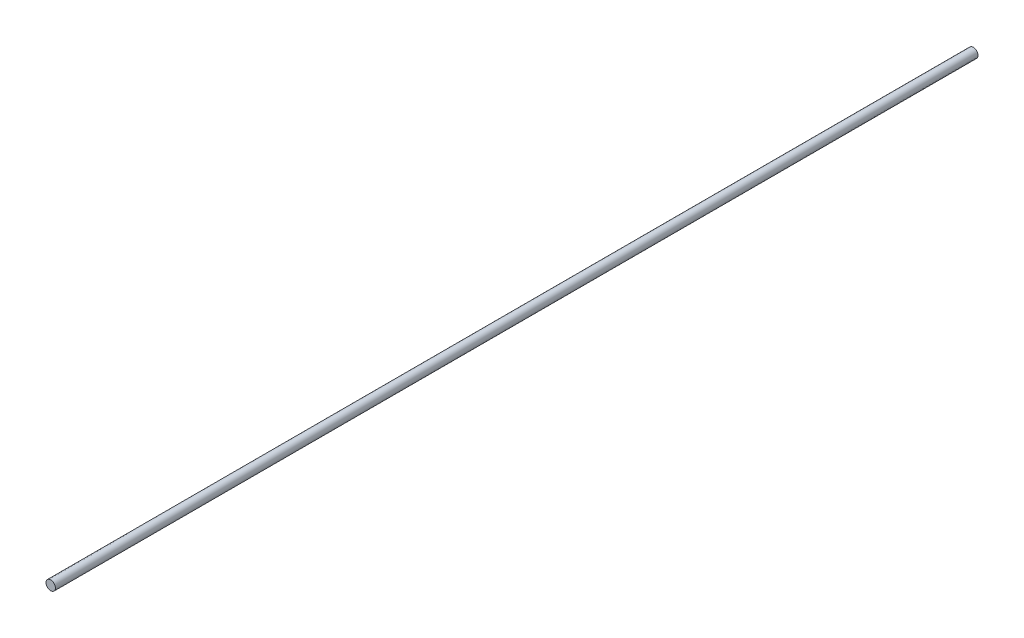
SolidWorks part; units mm, degrees
ref_plane "Front Plane" through (0, 0, 0) normal (0, 0, 1) x (1, 0, 0)
ref_plane "Top Plane" through (0, 0, 0) normal (0, 1, 0) x (1, 0, 0)
ref_plane "Right Plane" through (0, 0, 0) normal (1, 0, 0) x (0, 0, -1)
sketch "Sketch1" plane through (0, 0, 0) normal (0, 0, 1) x (1, 0, 0)
  circle A0 centre (0, 0) radius 2.5
extrude "Rod" add sketch "Sketch1" along normal blind 489
